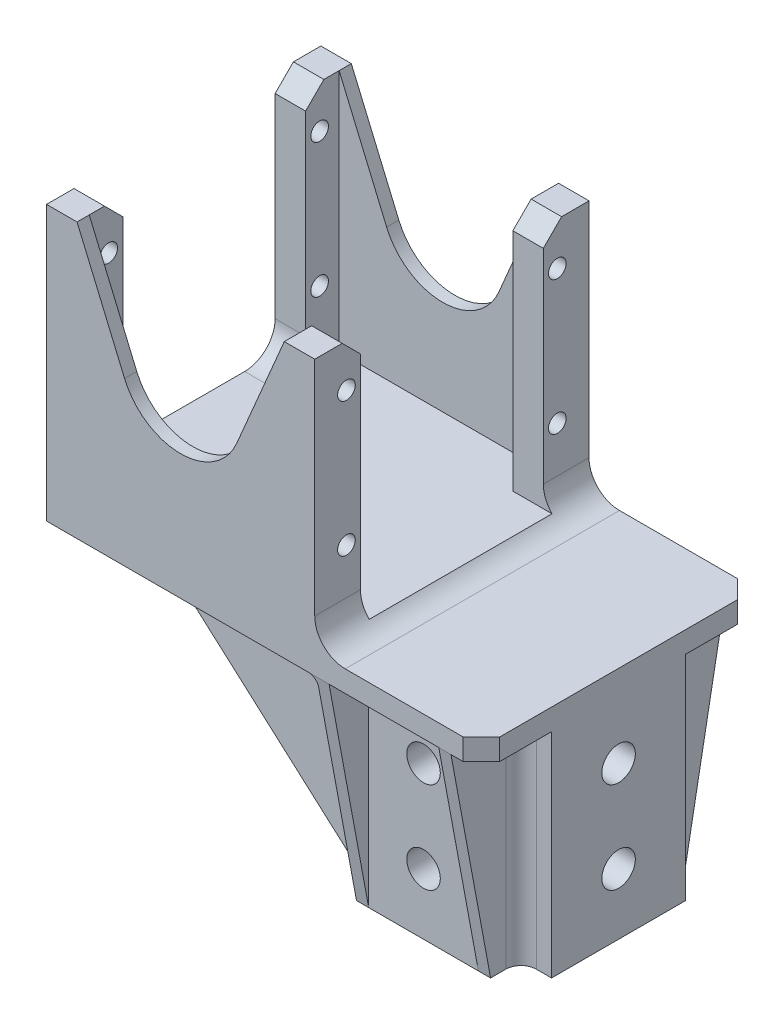
SolidWorks part; units mm, degrees
material "PLA"
ref_plane "Front Plane" through (0, 0, 0) normal (0, 0, 1) x (1, 0, 0)
ref_plane "Top Plane" through (0, 0, 0) normal (0, 1, 0) x (1, 0, 0)
ref_plane "Right Plane" through (0, 0, 0) normal (1, 0, 0) x (0, 0, -1)
sketch "Sketch2" plane through (0, 0, 0) normal (0, 0, 1) x (1, 0, 0)
  line L0 (12.8375, 22.5) -> (17.8375, 22.5) construction
  line L1 (-53.5125, 22.5) -> (17.8375, 22.5) construction
  line L2 (-17.8375, 22.5) -> (-17.8375, -22.5) construction
  line L3 (-53.5125, -22.5) -> (17.8375, -22.5)
  line L4 (17.8375, 22.5) -> (17.8375, -22.5) construction
  line L5 (-17.8375, 22.5) -> (17.8375, -22.5) construction
  line L6 (-17.8375, -22.5) -> (17.8375, 22.5) construction
  line L7 (-48.5125, 22.5) -> (12.8375, 22.5) construction
  line L8 (-17.8375, 22.5) -> (-17.8375, -17.5) construction
  line L9 (-48.5125, -17.5) -> (12.8375, -17.5) construction
  line L10 (12.8375, 22.5) -> (12.8375, -17.5) construction
  line L11 (-17.8375, 22.5) -> (12.8375, -17.5) construction
  line L12 (-17.8375, -17.5) -> (12.8375, 22.5) construction
  line L14 (-17.8375, -17.5) -> (-48.5125, 22.5) construction
  line L15 (-17.8375, 22.5) -> (-48.5125, -17.5) construction
  line L16 (-17.8375, -22.5) -> (-53.5125, 22.5) construction
  line L17 (-17.8375, 22.5) -> (-53.5125, -22.5) construction
  line L18 (-48.5125, 22.5) -> (-48.5125, -17.5)
  line L19 (-53.5125, 22.5) -> (-53.5125, -22.5)
  line L20 (-48.5125, 22.5) -> (-53.5125, 22.5)
  line L22 (-9.5125, -17.5) -> (-9.5125, 22.5)
  line L23 (-9.5125, 22.5) -> (-14.5125, 22.5)
  line L24 (-14.5125, 22.5) -> (-14.5125, -17.5)
  line L26 (17.8375, -17.5) -> (17.8375, -22.5)
  line L27 (-48.5125, -17.5) -> (-14.5125, -17.5)
  line L28 (-9.5125, -17.5) -> (17.8375, -17.5)
  point P4 (0, 0)
  point P8 (-2.5, 2.5)
  point P14 (-33.175, 2.5)
  point P15 (-35.675, 0)
  dimension "D1" = 5
  dimension "D2" = 40
  dimension "D3" = 27.35
  dimension "D4" = 5
  dimension "D5" = 34
  dimension "D6" = 5
extrude "Boss-Extrude1" add sketch "Sketch2" along normal blind 45
sketch "Sketch3" plane through (-53.5125, 0, 0) normal (1, 0, 0) x (0, 0, -1)
  line L0 (-5.2, 22.5) -> (-5.2, -22.5) construction
  line L2 (-39.8, 22.5) -> (-39.8, -22.5) construction
  line L4 (-37.5, 22.5) -> (-7.5, 22.5)
  line L5 (-37.5, 22.5) -> (-37.5, -17.5)
  line L6 (-37.5, -17.5) -> (-7.5, -17.5)
  line L7 (-7.5, 22.5) -> (-7.5, -17.5)
  line L8 (-37.5, 22.5) -> (-7.5, -17.5) construction
  line L9 (-37.5, -17.5) -> (-7.5, 22.5) construction
  line L10 (-45, 22.5) -> (0, 22.5) construction
  line L11 (-39.8, 15.5) -> (-5.2, 15.5) construction
  line L12 (-39.8, -6.5) -> (-5.2, -6.5) construction
  line L13 (-45, -22.5) -> (0, -22.5) construction
  circle A2 centre (-5.2, 15.5) radius 1.25 construction
  circle A3 centre (-5.2, -6.5) radius 1.25 construction
  circle A4 centre (-39.8, 15.5) radius 1.25 construction
  circle A5 centre (-39.8, -6.5) radius 1.25 construction
  point P10 (-22.5, 2.5)
  dimension "D4" = 2.3
  dimension "D7" = 2.5
  dimension "D5" = 2.5
  dimension "D6" = 2.5
  dimension "D9" = 2.5
  dimension "D8" = 22
  dimension "D1" = 30
  dimension "D2" = 5
  dimension "D3" = 2.3
  dimension "D10" = 11
extrude "Cut-Extrude1" cut sketch "Sketch3" along normal through all
sketch "Sketch4" plane through (0, -22.5, 0) normal (0, -1, 0) x (1, 0, 0)
  line L0 (-53.5125, 22.5) -> (17.8375, 22.5) construction
  line L1 (17.8375, 45) -> (17.8375, 0) construction
  line L3 (-53.5125, 45) -> (-53.5125, 0) construction
  line L10 (-8.4125, 32.75) -> (12.0875, 32.75)
  line L11 (-8.4125, 32.75) -> (-8.4125, 12.25)
  line L12 (-8.4125, 12.25) -> (12.0875, 12.25)
  line L13 (12.0875, 32.75) -> (12.0875, 12.25)
  line L14 (-8.4125, 32.75) -> (12.0875, 12.25) construction
  line L15 (-8.4125, 12.25) -> (12.0875, 32.75) construction
  line L16 (-14.1625, 38.5) -> (17.8375, 38.5)
  line L17 (-14.1625, 38.5) -> (-14.1625, 6.5)
  line L18 (-14.1625, 6.5) -> (17.8375, 6.5)
  line L19 (17.8375, 38.5) -> (17.8375, 6.5)
  line L20 (-14.1625, 38.5) -> (17.8375, 6.5) construction
  line L21 (-14.1625, 6.5) -> (17.8375, 38.5) construction
  circle A0 centre (1.8375, 22.5) radius 2.5
  point P18 (1.8375, 22.5)
  point P23 (1.8375, 22.5)
  dimension "D1" = 5
  dimension "D2" = 20.5
  dimension "D3" = 20.5
  dimension "D4" = 32
extrude "Boss-Extrude2" add sketch "Sketch4" along normal blind 35 contours L19 L16 L17 L18 L10 L13 L12 L11 region at (1.8375, -22.5, 38.0475)
sketch "Sketch5" plane through (0, 0, 38.5) normal (0, 0, 1) x (1, 0, 0)
  line L0 (1.8375, -22.5) -> (1.8375, -57.5) construction
  line L3 (-14.1625, -22.5) -> (17.8375, -22.5) construction
  line L4 (-14.1625, -57.5) -> (17.8375, -57.5) construction
  circle A0 centre (1.8375, -32.5) radius 2.5 construction
  circle A1 centre (1.8375, -47.5) radius 2.5 construction
  dimension "D2" = 5
  dimension "D3" = 5
  dimension "D4" = 10
  dimension "D1" = 15
sketch "Sketch6" plane through (0, -57.5, 0) normal (0, -1, 0) x (-1, 0, 0)
  line L1 (14.1625, -38.5) -> (9.1625, -38.5)
  line L2 (14.1625, -38.5) -> (14.1625, -33.5)
  line L3 (14.1625, -33.5) -> (9.1625, -33.5)
  line L4 (9.1625, -38.5) -> (9.1625, -33.5)
  line L5 (14.1625, -38.5) -> (9.1625, -33.5) construction
  line L6 (14.1625, -33.5) -> (9.1625, -38.5) construction
  line L7 (-17.8375, -38.5) -> (-12.8375, -38.5)
  line L8 (-17.8375, -38.5) -> (-17.8375, -33.5)
  line L9 (-17.8375, -33.5) -> (-12.8375, -33.5)
  line L10 (-12.8375, -38.5) -> (-12.8375, -33.5)
  line L11 (-17.8375, -38.5) -> (-12.8375, -33.5) construction
  line L12 (-17.8375, -33.5) -> (-12.8375, -38.5) construction
  line L13 (-17.8375, -6.5) -> (-12.8375, -6.5)
  line L14 (-17.8375, -6.5) -> (-17.8375, -11.5)
  line L15 (-17.8375, -11.5) -> (-12.8375, -11.5)
  line L16 (-12.8375, -6.5) -> (-12.8375, -11.5)
  line L17 (-17.8375, -6.5) -> (-12.8375, -11.5) construction
  line L18 (-17.8375, -11.5) -> (-12.8375, -6.5) construction
  line L19 (14.1625, -6.5) -> (9.1625, -6.5)
  line L20 (14.1625, -6.5) -> (14.1625, -11.5)
  line L21 (14.1625, -11.5) -> (9.1625, -11.5)
  line L22 (9.1625, -6.5) -> (9.1625, -11.5)
  line L23 (14.1625, -6.5) -> (9.1625, -11.5) construction
  line L24 (14.1625, -11.5) -> (9.1625, -6.5) construction
  point P4 (11.6625, -36)
  point P11 (-15.3375, -36)
  point P18 (-15.3375, -9)
  point P25 (11.6625, -9)
  dimension "D1" = 5
  dimension "D2" = 5
  dimension "D3" = 5
  dimension "D4" = 5
extrude "Cut-Extrude4" cut sketch "Sketch6" against normal up to surface (35 mm away) up to face at (-8, -22.5, 22.5)
sketch "Sketch9" plane through (0, 0, 33.5) normal (0, 0, 1) x (1, 0, 0)
  line L0 (-14.1625, -57.5) -> (-53.5125, -22.5)
  line L1 (-53.5125, -22.5) -> (17.8375, -22.5) construction
  line L2 (-53.5125, -22.5) -> (17.8375, -22.5) construction
rib "Rib1" sketch "Sketch9" sketch "Sketch9" thickness 2 extrusion direction parallel to sketch draft on no parameters "D1"=2
pattern_linear "LPattern1" count 2 spacing 20 along (0, 0, -1) of "Rib1"
sketch "Sketch14" plane through (12.8375, 0, 0) normal (1, 0, 0) x (0, 0, -1)
  line L0 (-6.5, -57.5) -> (0, -22.5)
rib "Rib6" sketch "Sketch14" sketch "Sketch14" thickness 2 extrusion direction parallel to sketch draft on no parameters "D1"=2
sketch "Sketch15" plane through (-9.1625, 0, 0) normal (-1, 0, 0) x (0, 0, 1)
  line L0 (6.5, -57.5) -> (0, -22.5)
rib "Rib7" sketch "Sketch15" sketch "Sketch15" thickness 2 extrusion direction parallel to sketch draft on no parameters "D1"=2
fillet "Fillet2" radius 5 3 edges at (-14.1625, -22.5, 22.5) (1.8375, -22.5, 6.5) (1.8375, -22.5, 38.5)
fillet "Fillet3" radius 5 2 edges at (-9.5125, -17.5, 3.75) (-9.5125, -17.5, 41.25)
sketch "Sketch17" plane through (0, 0, 45) normal (0, 0, 1) x (1, 0, 0)
  line L0 (-48.5125, 22.5) -> (-31.5125, -17.5)
  line L1 (-14.5125, -17.5) -> (-48.5125, -17.5) construction
rib "Rib10" sketch "Sketch17" sketch "Sketch17" thickness 2 extrusion direction parallel to sketch draft on no parameters "D1"=2
sketch "Sketch18" plane through (0, 0, 45) normal (0, 0, 1) x (1, 0, 0)
  line L0 (-31.5125, -17.5) -> (-14.5125, 22.5)
rib "Rib11" sketch "Sketch18" sketch "Sketch18" thickness 2 extrusion direction parallel to sketch draft on no parameters "D1"=2
fillet "Fillet4" radius 10 1 edges at (-31.5125, -17.5, 44)
pattern_linear "LPattern2" count 2 spacing 43 along (0, 0, -1) of "Fillet4", "Rib11", "Rib10"
hole_wizard "M5 Clearance Hole2" positions "Sketch20" profile "Sketch22" hole size "M5" standard "ISO"
sketch "Sketch20" plane through (0, 0, 38.5) normal (0, 0, 1) x (1, 0, 0)
  point P0 (1.8375, -32.5)
  point P3 (1.8375, -47.5)
sketch "Sketch22" plane through (1.8375, -32.5, 38.5) normal (1, 0, 0) x (0, -1, 0)
  line L0 (0, 0) -> (0, 7.6524)
  line L1 (0, 7.6524) -> (2.75, 6)
  line L2 (2.75, 6) -> (2.75, 0)
  line L5 (2.75, 0) -> (0, 0)
  line L10 (0, 7.6524) -> (-2.75, 6) construction
  line L11 (0, -6.35) -> (0, 107.95) construction
  dimension "Hole Dia." = 5.5
  dimension "Hole Depth" = 6
  dimension "Drill Angle" = 118
hole_wizard "M2.5 Clearance Hole1" positions "Sketch23" profile "Sketch24" hole size "M2.5" standard "ISO" end condition through all
sketch "Sketch23" plane through (-53.5125, 0, 0) normal (-1, 0, 0) x (0, 0, 1)
  point P0 (5.2, 15.5)
  point P3 (39.8, 15.5)
  point P6 (39.8, -6.5)
  point P9 (5.2, -6.5)
sketch "Sketch24" plane through (-53.5125, 15.5, 5.2) normal (0, 1, 0) x (0, 0, 1)
  line L0 (0, 0) -> (0, 71.35)
  line L1 (0, 71.35) -> (1.45, 71.35)
  line L2 (1.45, 71.35) -> (1.45, 0)
  line L5 (1.45, 0) -> (0, 0)
  line L11 (0, -6.35) -> (0, 107.95) construction
  dimension "Thru Hole Dia." = 2.9
  dimension "Thru Hole Depth" = 71.35
fillet "Fillet5" radius 2.5 4 edges at (-9.1625, -40, 11.5) (-9.1625, -40, 33.5) (12.8375, -40, 33.5) (12.8375, -40, 11.5)
extrude "Boss-Extrude4" add sketch "Sketch4<4>" along normal blind 8 contours A0 region at (1.8375, -22.5, 22.5)
sketch "Sketch4<4>" plane through (0, -22.5, 0) normal (0, -1, 0) x (1, 0, 0) same geometry as "Sketch4"
pattern_circular "CirPattern1" count 4 every 90 about axis through (1.8375, -30.5, 22.5) along (0, -1, 0) of "M5 Clearance Hole2"
ref_axis "Axis2" through (1.8375, -30.5, 22.5) along (0, 1, 0)
ref_plane "Plane1" through (0, 0, 22.5) normal (0, 0, 1) x (1, 0, 0)
mirror "Mirror1" about plane through (0, 0, 22.5) normal (0, 0, 1) of "Rib6", "Rib7"
chamfer "Chamfer1" distance 3 angle 45 6 edges at (17.8375, -20, 0) (17.8375, -20, 45) (-51.0125, 22.5, 37.5) (-51.0125, 22.5, 7.5) (-12.0125, 22.5, 7.5) (-12.0125, 22.5, 37.5)
fillet "Fillet6" radius 5 2 edges at (-51.0125, -17.5, 37.5) (-51.0125, -17.5, 7.5)
fillet "Fillet7" radius 1.5 12 edges at (-9.1625, -22.5, 4.5) (-9.8947, -22.5, 10.7678) (-14.1625, -42.5, 13.5) (-15.627, -23.9645, 13.5) (-14.1625, -42.5, 31.5) (-15.627, -23.9645, 31.5) (-9.1625, -22.5, 40.5) (-9.8947, -22.5, 34.2322) (-32.5875, -22.5, 11.5) (-36.3375, -22.5, 13.5) (-36.3375, -22.5, 31.5) (-32.5875, -22.5, 33.5)
sketch "Sketch27" plane through (0, 0, 45) normal (0, 0, 1) x (1, 0, 0)
  line L0 (17.8375, -17.5) -> (17.8375, -22.5) construction
  line L1 (-9.5125, -12.5) -> (17.8375, -12.5)
  line L2 (-9.5125, -12.5) -> (-9.5125, -19)
  line L3 (-9.5125, -19) -> (17.8375, -19)
  line L4 (17.8375, -12.5) -> (17.8375, -19)
  line L5 (10.8375, -22.5) -> (12.8375, -22.5) construction
  dimension "D1" = 3.5
extrude "Cut-Extrude6" cut sketch "Sketch27" against normal through all
fillet "Fillet8" radius 5 1 edges at (-9.5125, -19, 22.5)
